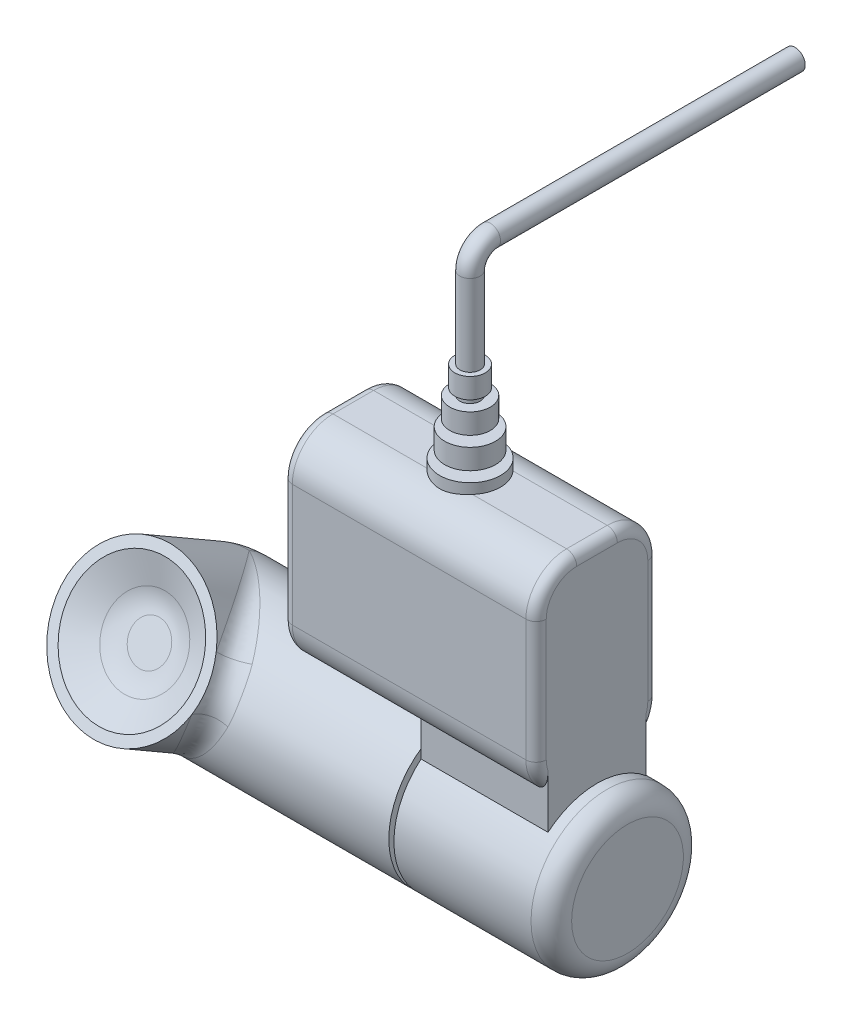
SolidWorks part; units mm, degrees
ref_plane "Front Plane" through (0, 0, 0) normal (0, 0, 1) x (1, 0, 0)
ref_plane "Top Plane" through (0, 0, 0) normal (0, 1, 0) x (1, 0, 0)
ref_plane "Right Plane" through (0, 0, 0) normal (1, 0, 0) x (0, 0, -1)
sketch "Sketch1" plane through (0, 0, 0) normal (0, 0, 1) x (1, 0, 0)
  line L1 (-12.5, -10) -> (12.5, -10)
  line L2 (-12.5, -10) -> (-12.5, 10)
  line L3 (-12.5, 10) -> (12.5, 10)
  line L4 (12.5, -10) -> (12.5, 10)
  line L5 (-12.5, -10) -> (12.5, 10) construction
  line L6 (-12.5, 10) -> (12.5, -10) construction
  point P0 (0, 0)
  dimension "D1" = 25
  dimension "D2" = 20
extrude "Boss-Extrude1" add sketch "Sketch1" along normal mid plane 12
fillet "Fillet1" radius 4 4 edges at (0, -10, 6) (0, -10, -6) (0, 10, 6) (0, 10, -6)
sketch "Sketch2" plane through (0, 0, 0) normal (1, 0, 0) x (0, 0, -1)
  line L0 (-2, -10) -> (2, -10) construction
  line L1 (-4.8284, -8.8284) -> (-4.8284, -12.261)
  line L2 (4.8284, -8.8284) -> (4.8284, -12.261)
  line L3 (-4.8284, -8.8284) -> (4.8284, -8.8284)
  circle A0 centre (0, -18) radius 7.5
  arc A1 (-6, -6) -> (-2, -10) centre (-2, -6) ccw construction
  arc A2 (2, -10) -> (6, -6) centre (2, -6) ccw construction
  point P2 (0, -10)
  dimension "D1" = 15
  dimension "D2" = 0.5
extrude "Boss-Extrude2" add sketch "Sketch2" along normal up to vertex (12.5 mm away) contours A0 | A0 L2 L3 L1 region at (0, -10.0017, 0) region at (0, -18, 0) up to point (12.5, -6, 6)
extrude "Boss-Extrude4" add sketch "Sketch2<3>" along normal blind 3 from surface contours A0 starting at face at (12.5, -3.3994, 0)
sketch "Sketch2<3>" plane through (0, 0, 0) normal (1, 0, 0) x (0, 0, -1) same geometry as "Sketch2"
fillet "Fillet2" radius 2 1 edges at (15.5, -18, 7.5)
fillet "Fillet3" radius 1 15 edges at (-12.5, 8.8284, 4.8284) (-12.5, 10, 0) (-12.5, 8.8284, -4.8284) (-12.5, 0, -6) (-12.5, -8.8284, -4.8284) (-12.5, -10, 0) (-12.5, -8.8284, 4.8284) (12.5, -7.5307, 5.6955) (12.5, -7.5307, -5.6955) (12.5, 0, -6) (12.5, 8.8284, -4.8284) (12.5, 10, 0) (12.5, 8.8284, 4.8284) (-12.5, 0, 6) (12.5, 0, 6)
sketch "Sketch3" plane through (0, 0, 0) normal (-1, 0, 0) x (0, 0, 1)
  circle A0 centre (0, -18) radius 5
  dimension "D1" = 10
extrude "Boss-Extrude3" add sketch "Sketch3" along normal blind 0.5
sketch "Sketch5" plane through (-0.5, 0, 0) normal (-1, 0, 0) x (0, 0, 1)
  circle A0 centre (0, -18) radius 7.5 construction
  circle A1 centre (0, -18) radius 7.5
extrude "Boss-Extrude5" add sketch "Sketch5" along normal blind 25
sketch "Sketch6" plane through (0, 0, 0) normal (0, 0, 1) x (1, 0, 0)
  line L0 (-25.5, -10.5) -> (-25.5, -25.5) construction
  line L1 (-25.5, -10.5) -> (-25.5, -25.5)
  line L2 (-0.5, -10.5) -> (-25.5, -10.5) construction
  arc A0 (-25.5, -25.5) -> (-25.5, -10.5) centre (-25.5, -18) ccw
revolve "Revolve1" add sketch "Sketch6" angle 360 about L1
sketch3d "3DSketch2"
  line L0 (-25.5, -18, 0) -> (-25.5, -8, 17.3205)
  line L1 (-25.5, -18, 0) -> (-25.5, 2, 0) construction
  line L2 (-25.5, -8, 17.3205) -> (-25.5, -8, 0) construction
  circle A0 centre (-25.5, -18, 0) radius 7.5 construction
  point P4 (-33, -18, 0)
  dimension "D1" = 60
  dimension "D2" = 20
ref_plane "Plane1" through (-25.5, -18, 0) normal (0, 0.5, 0.866) x (1, 0, 0)
sketch "Sketch7" plane through (0, -2.4115, -9) normal (0, 0.5, 0.866) x (1, 0, 0)
  circle A0 centre (-25.5, -18) radius 7.5
  arc A1 (-25.5, -10.5) -> (-25.5, -25.5) centre (-25.5, -18) ccw construction
extrude "Boss-Extrude6" add sketch "Sketch7" along normal blind 9
fillet "Fillet5" radius 2 1 edges at (-18, -14.25, 6.4952)
sketch "Sketch8" plane through (0, 0, 0) normal (0, 0.5, 0.866) x (1, 0, 0)
  circle A0 centre (-25.5, -15.5885) radius 6.5
  dimension "D1" = 13
extrude "Cut-Extrude2" cut sketch "Sketch8" against normal blind 2 draft 60
sketch "Sketch9" plane through (0, 0, 0) normal (1, 0, 0) x (0, 0, -1)
  line L0 (0, 9) -> (0, 19)
  line L2 (0, 19) -> (-1.5, 19)
  line L3 (-1.5, 19) -> (-1.5, 17)
  line L4 (-1.5, 17) -> (-1, 17)
  line L5 (-1, 17) -> (-1, 16.3333)
  line L6 (-1, 16.3333) -> (-2, 16.3333)
  line L7 (-2, 16.3333) -> (-2, 14.3333)
  line L8 (-2, 14.3333) -> (-1, 14.3333)
  line L9 (-1, 14.3333) -> (-1, 13.6667)
  line L10 (-1, 13.6667) -> (-2.5, 13.6667)
  line L11 (-2.5, 13.6667) -> (-2.5, 11.6667)
  line L12 (-2.5, 11.6667) -> (-1, 11.6667)
  line L13 (-1, 11.6667) -> (-1, 11)
  line L14 (-1, 11) -> (-3, 11)
  line L15 (-3, 11) -> (-3, 9)
  line L16 (-3, 9) -> (0, 9)
  line L17 (2, 9) -> (-2, 9) construction
  dimension "D1" = 10
  dimension "D2" = 2
  dimension "D3" = 0.5
  dimension "D4" = 0.5
  dimension "D5" = 0.5
  dimension "D6" = 1
  dimension "D7" = 0.5
  dimension "D8" = 2
revolve "Revolve2" add sketch "Sketch9" angle 360 about L0
sketch "Sketch10" plane through (0, 0, 0) normal (1, 0, 0) x (0, 0, -1)
  line L0 (0, 19) -> (0, 27)
  line L1 (1.5, 19) -> (-1.5, 19) construction
  line L2 (2, 29) -> (32, 29)
  arc A0 (2, 29) -> (0, 27) centre (2, 27) ccw
  dimension "D1" = 2
  dimension "D2" = 10
  dimension "D3" = 30
sketch "Sketch11" plane through (0, 19, 0) normal (0, 1, 0) x (1, 0, 0)
  circle A0 centre (0, 0) radius 1
  dimension "D1" = 2
sweep "Sweep1" add profiles "Sketch11" path "Sketch10"
fillet "Fillet6" radius 4 1 edges at (-25.5, -17.1292, 7.5801)
